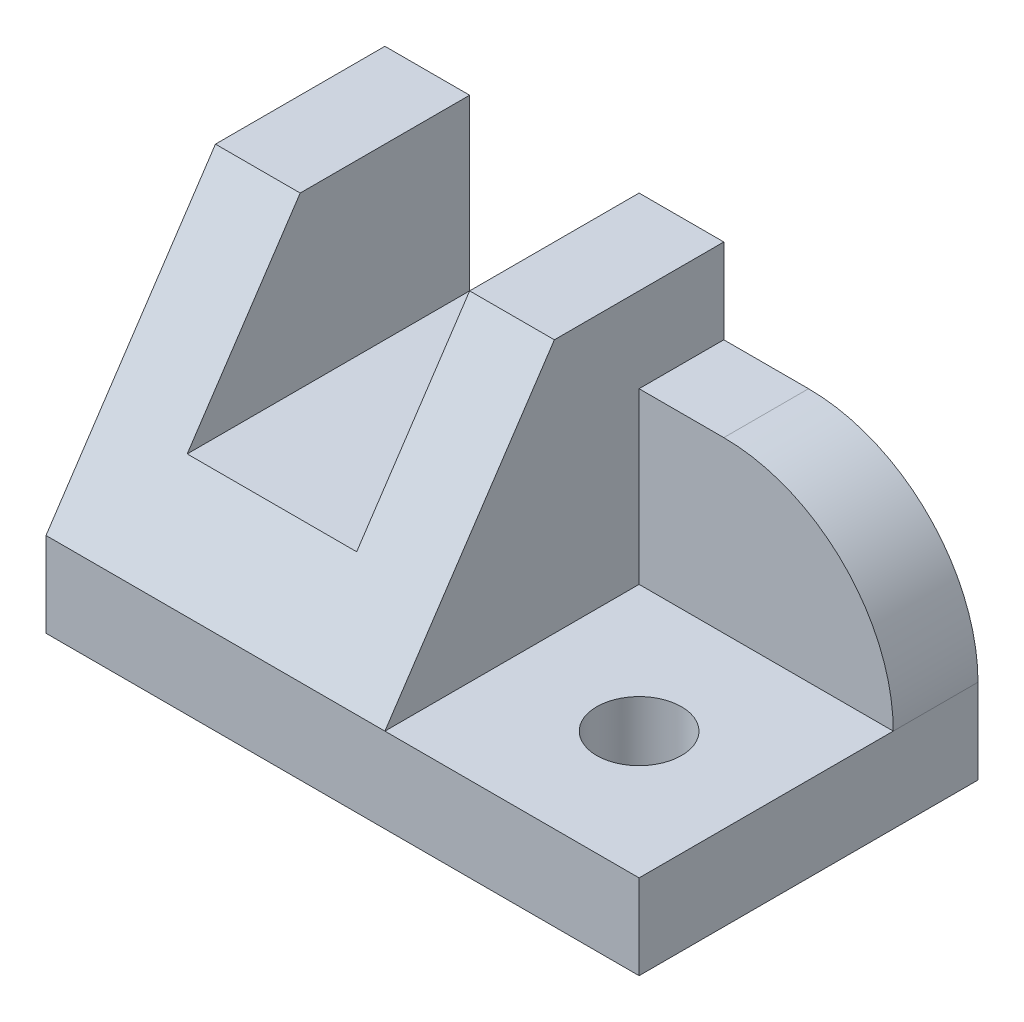
SolidWorks part; units mm, degrees
ref_plane "Front Plane" through (0, 0, 0) normal (0, 0, 1) x (1, 0, 0)
ref_plane "Top Plane" through (0, 0, 0) normal (0, 1, 0) x (1, 0, 0)
ref_plane "Right Plane" through (0, 0, 0) normal (1, 0, 0) x (0, 0, -1)
ref_plane "Plane1" through (0, 0, 0) normal (-1, 0, 0) x (0, -1, 0)
sketch "Sketch1" plane through (0, 0, 0) normal (-1, 0, 0) x (0, -1, 0)
  line L0 (-10, 0) -> (-40, -20)
  line L1 (-40, -20) -> (-10, -20)
  line L2 (-10, -20) -> (-10, 0)
  dimension "D1" = 30
  dimension "Width" = 20
extrude "Boss-Extrude1" add sketch "Sketch1" against normal blind 40
sketch "Sketch2" plane through (0, 0, -20) normal (0, 0, -1) x (-1, 0, 0)
  line L0 (-40, 40) -> (0, 40)
  line L1 (0, 40) -> (0, 10)
  line L2 (0, 10) -> (-40, 10)
  line L3 (-40, 10) -> (-40, 40)
extrude "Boss-Extrude2" add sketch "Sketch2" along normal blind 20
sketch "Sketch3" plane through (40, 0, 0) normal (1, 0, 0) x (0, 0, -1)
  line L0 (40, 10) -> (0, 10)
  line L1 (0, 10) -> (20, 40)
  line L2 (20, 40) -> (40, 40)
  line L3 (40, 40) -> (40, 10)
extrude "Boss-Extrude3" add sketch "Sketch3" along normal blind 30
sketch "Sketch4" plane through (70, 0, 0) normal (1, 0, 0) x (0, 0, -1)
  line L0 (20, 40) -> (0, 10)
  line L1 (0, 10) -> (30, 10)
  line L2 (30, 10) -> (30, 30)
  line L3 (30, 30) -> (40, 30)
  line L4 (40, 30) -> (40, 40)
  line L5 (40, 40) -> (20, 40)
extrude "Cut-Extrude1" cut sketch "Sketch4" against normal blind 30
sketch "Sketch5" plane through (0, 10, 0) normal (0, -1, 0) x (1, 0, 0)
  line L0 (70, 0) -> (70, -40)
  line L1 (70, -40) -> (0, -40)
  line L2 (0, -40) -> (0, 0)
  line L3 (0, 0) -> (70, 0)
extrude "Boss-Extrude4" add sketch "Sketch5" along normal blind 10
sketch "Sketch6" plane through (0, 0, -40) normal (0, 0, -1) x (-1, 0, 0)
  line L0 (-30, 40) -> (-30, 20)
  line L1 (-30, 20) -> (-10, 20)
  line L2 (-10, 20) -> (-10, 40)
  line L3 (-10, 40) -> (-30, 40)
extrude "Cut-Extrude2" cut sketch "Sketch6" against normal through all
hole_wizard "Ø10.0 (10) Diameter Hole1" positions "Sketch8" profile "Sketch7" hole size "Ø10.0" standard "ANSI Metric"
sketch "Sketch8" plane through (0, 0, 0) normal (0, -1, 0) x (-1, 0, 0)
  point P0 (-55, 15)
sketch "Sketch7" plane through (55, 0, -15) normal (1, 0, 0) x (0, 0, -1)
  line L0 (0, 0) -> (0, 40)
  line L1 (0, 40) -> (5, 40)
  line L2 (5, 40) -> (5, 0)
  line L5 (5, 0) -> (0, 0)
  line L11 (0, -6.35) -> (0, 107.95) construction
  dimension "Thru Hole Dia." = 10
  dimension "Thru Hole Depth" = 40
fillet "Fillet1" radius 20 1 edges at (70, 30, -35) tangent propagation no
